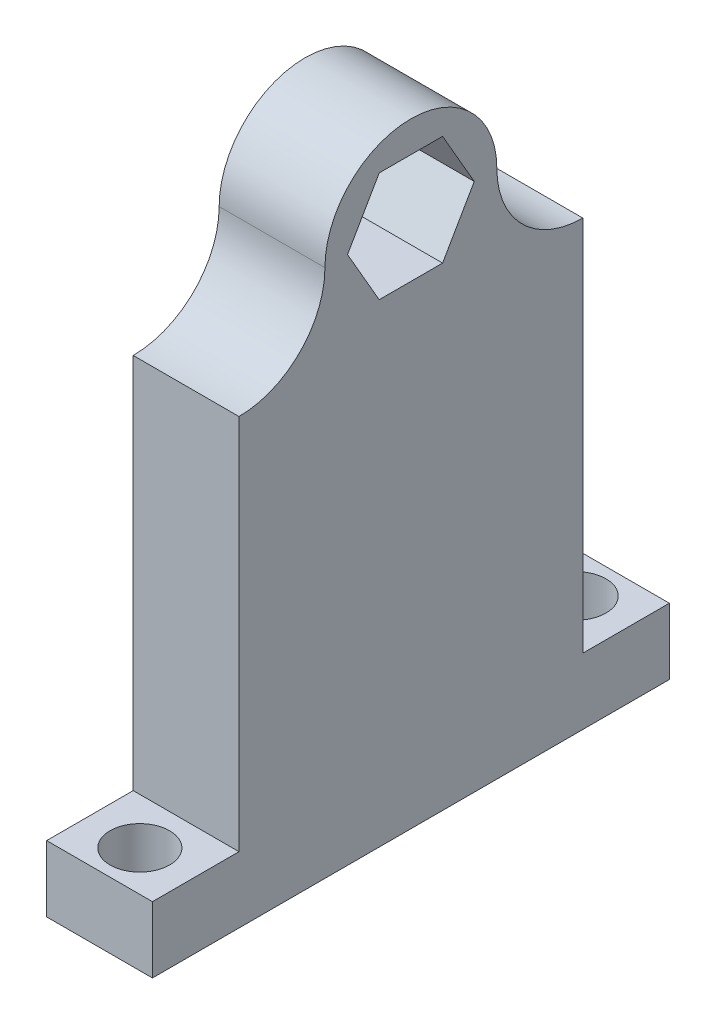
SolidWorks part; units mm, degrees
ref_plane "Спереди" through (0, 0, 0) normal (0, 0, 1) x (1, 0, 0)
ref_plane "Сверху" through (0, 0, 0) normal (0, 1, 0) x (1, 0, 0)
ref_plane "Справа" through (0, 0, 0) normal (1, 0, 0) x (0, 0, -1)
sketch "Эскиз1" plane through (0, 0, 0) normal (1, 0, 0) x (0, 0, -1)
  line L6 (-6.5, 0) -> (6.5, 0) construction
  line L12 (-13, -6.5) -> (-13, -11.5)
  line L13 (13, -6.5) -> (13, -11.5)
  line L15 (-13, -11.5) -> (13, -11.5)
  arc A0 (6.5, 0) -> (-6.5, 0) centre (0, 0) ccw
  arc A1 (-13, -6.5) -> (-6.5, 0) centre (-13, 0) ccw
  arc A2 (6.5, 0) -> (13, -6.5) centre (13, 0) ccw
  point P4 (0, 0)
  point P6 (12.1441, -1.8609)
  point P7 (0, -39.795)
  point P9 (0, 6.5)
  dimension "D1" = 13
  dimension "D4" = 13
  dimension "D5" = 13
  dimension "D2" = 5
extrude "Бобышка-Вытянуть1" add sketch "Эскиз1" along normal blind 8
sketch "Эскиз2" plane through (8, 0, 0) normal (1, 0, 0) x (0, 0, -1)
  line L1 (4.792, 0) -> (2.396, 4.15)
  line L2 (2.396, 4.15) -> (-2.396, 4.15)
  line L3 (-2.396, 4.15) -> (-4.792, 0)
  line L4 (-4.792, 0) -> (-2.396, -4.15)
  line L5 (-2.396, -4.15) -> (2.396, -4.15)
  line L6 (2.396, -4.15) -> (4.792, 0)
  circle A0 centre (0, 0) radius 4.15 construction
  dimension "D1" = 8.3
extrude "Вырез-Вытянуть1" cut sketch "Эскиз2" against normal through all
sketch "Эскиз4" plane through (0, -11.5, 0) normal (0, -1, 0) x (1, 0, 0)
  line L8 (0, 13) -> (0, -13)
  line L9 (0, -13) -> (8, -13)
  line L10 (8, -13) -> (8, 13)
  line L11 (8, 13) -> (0, 13)
  line L12 (0, 13) -> (0, -13)
  line L13 (0, -13) -> (8, -13)
  line L14 (8, -13) -> (8, 13)
  line L15 (8, 13) -> (0, 13)
  dimension "D1" = 0
extrude "Бобышка-Вытянуть2" add sketch "Эскиз4" along normal up to surface (28.5 mm away)
sketch "Эскиз5" plane through (0, -40, 0) normal (0, -1, 0) x (1, 0, 0)
  line L0 (0, 13) -> (0, -13) construction
  line L1 (0, 19.5455) -> (8, 19.5455)
  line L2 (0, 19.5455) -> (0, -19.5455)
  line L3 (0, -19.5455) -> (8, -19.5455)
  line L4 (8, 19.5455) -> (8, -19.5455)
  line L5 (8, -13) -> (8, 13) construction
  line L6 (-6134.4302, -19.5455) -> (-6674.4302, -19.5455) construction
  line L7 (-6134.4302, 19.5455) -> (-6674.4302, 19.5455) construction
  line L8 (4, -16.5) -> (4, 16.5) construction
  line L9 (8, -19.5455) -> (0, 19.5455) construction
  line L10 (0, -19.5455) -> (8, 19.5455) construction
  circle A0 centre (4, -16.5) radius 2.25
  circle A1 centre (4, 16.5) radius 2.25
  point P16 (4, 0)
  point P17 (8, 0)
  point P18 (4, 0)
  dimension "D1" = 4.5
  dimension "D2" = 4.5
  dimension "D3" = 33
extrude "Бобышка-Вытянуть3" add sketch "Эскиз5" against normal blind 5
